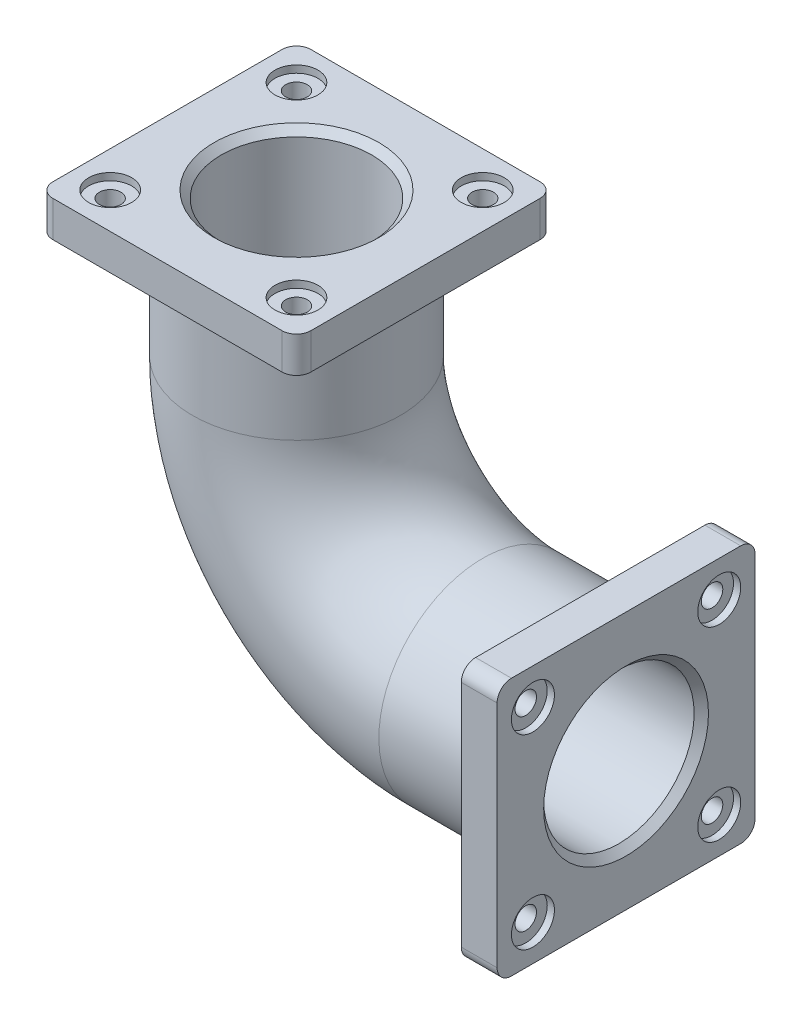
SolidWorks part; units mm, degrees
ref_plane "Front Plane" through (0, 0, 0) normal (0, 0, 1) x (1, 0, 0)
ref_plane "Top Plane" through (0, 0, 0) normal (0, 1, 0) x (1, 0, 0)
ref_plane "Right Plane" through (0, 0, 0) normal (1, 0, 0) x (0, 0, -1)
sketch "Sketch1" plane through (0, 0, 0) normal (0, 0, 1) x (1, 0, 0)
  line L0 (0, 260) -> (0, 410)
  line L1 (260, 0) -> (410, 0)
  line L2 (260, 105) -> (410, 105)
  line L3 (105, 260) -> (105, 410)
  line L4 (260, -105) -> (410, -105)
  line L5 (-105, 260) -> (-105, 410)
  line L6 (-105, 410) -> (105, 410) construction
  line L7 (410, 105) -> (410, -104.7476) construction
  arc A0 (0, 260) -> (260, 0) centre (260, 260) ccw
  arc A1 (105, 260) -> (260, 105) centre (260, 260) ccw
  arc A2 (-105, 260) -> (260, -105) centre (260, 260) ccw
  point P5 (0, 0)
  dimension "D1" = 260
  dimension "D2" = 150
  dimension "D3" = 150
  dimension "D4" = 105
  dimension "D5" = 105
ref_plane "Plane1" through (0, 410, 0) normal (0, 1, 0) x (1, 0, 0)
sketch "Sketch2" plane through (0, 410, 0) normal (0, 1, 0) x (1, 0, 0)
  line L1 (-180, 180) -> (180, 180)
  line L2 (-180, 180) -> (-180, -180)
  line L3 (-180, -180) -> (180, -180)
  line L4 (180, 180) -> (180, -180)
  line L5 (-180, 180) -> (180, -180) construction
  line L6 (-180, -180) -> (180, 180) construction
  circle A0 centre (0, 0) radius 105
  circle A1 centre (0, 0) radius 145
  circle A2 centre (130, 130) radius 30
  circle A3 centre (130, 130) radius 15
  circle A4 centre (130, -130) radius 15
  circle A5 centre (130, -130) radius 30
  circle A6 centre (-130, -130) radius 15
  circle A7 centre (-130, -130) radius 30
  circle A8 centre (-130, 130) radius 15
  circle A9 centre (-130, 130) radius 30
  point P27 (0, 0)
  dimension "D1" = 210
  dimension "D2" = 290
  dimension "D5" = 60
  dimension "D6" = 30
  dimension "D3" = 360
  dimension "D4" = 360
  dimension "D7" = 50
  dimension "D9" = 260
  dimension "D10" = 260
  dimension "D8" = 4
ref_plane "Plane2" through (410, 0, 0) normal (1, 0, 0) x (0, 0, -1)
sketch "Sketch3" plane through (410, 0, 0) normal (1, 0, 0) x (0, 0, -1)
  line L1 (-180, 180) -> (180, 180)
  line L2 (-180, 180) -> (-180, -180)
  line L3 (-180, -180) -> (180, -180)
  line L4 (180, 180) -> (180, -180)
  line L5 (-180, 180) -> (180, -180) construction
  line L6 (-180, -180) -> (180, 180) construction
  circle A0 centre (0, 0) radius 105
  circle A1 centre (0, 0) radius 145
  circle A2 centre (130, 130) radius 30
  circle A3 centre (130, 130) radius 15
  circle A4 centre (130, -130) radius 15
  circle A5 centre (130, -130) radius 30
  circle A6 centre (-130, -130) radius 15
  circle A7 centre (-130, -130) radius 30
  circle A8 centre (-130, 130) radius 15
  circle A9 centre (-130, 130) radius 30
  point P23 (0, 0)
  dimension "D1" = 210
  dimension "D2" = 290
  dimension "D5" = 60
  dimension "D6" = 30
  dimension "D3" = 360
  dimension "D4" = 360
  dimension "D7" = 50
  dimension "D9" = 260
  dimension "D10" = 260
  dimension "D8" = 4
extrude "Boss-Extrude1" add sketch "Sketch3" along normal blind 50 contours L4 L1 L2 L3 A9 A7 A5 A2 A1 | A1 A0 region at (410, 174.9088, 0) region at (410, 0, 140.8988)
extrude "Boss-Extrude2" add sketch "Sketch3<3>" along normal blind 40 contours A9 A8 | A2 A3 | A7 A6 | A5 A4 region at (410, 130, -100.8485) region at (410, -130, -100.8485) region at (410, -130, 159.1515) region at (410, 130, 159.1515)
sketch "Sketch3<3>" plane through (410, 0, 0) normal (1, 0, 0) x (0, 0, -1) same geometry as "Sketch3"
extrude "Boss-Extrude3" add sketch "Sketch2" along normal blind 50 contours L4 L1 L2 L3 A9 A7 A5 A2 A1 | A1 A0 region at (0, 410, -174.9088) region at (-140.8988, 410, 0)
extrude "Boss-Extrude4" add sketch "Sketch2<3>" along normal blind 40 contours A7 A6 | A9 A8 | A5 A4 | A2 A3 region at (100.8485, 410, -130) region at (100.8485, 410, 130) region at (-159.1515, 410, 130) region at (-159.1515, 410, -130)
sketch "Sketch2<3>" plane through (0, 410, 0) normal (0, 1, 0) x (1, 0, 0) same geometry as "Sketch2"
ref_plane "Plane3" through (410, 0, 0) normal (-1, 0, 0) x (0, 0, 1)
sketch "Sketch4" plane through (410, 0, 0) normal (-1, 0, 0) x (0, 0, 1)
  circle A1 centre (0, 0) radius 145
  dimension "D1" = 290
sweep "Sweep1" add profiles "Sketch4" path "Sketch1"
sketch "Sketch5" plane through (0, 410, 0) normal (0, 1, 0) x (1, 0, 0)
  circle A0 centre (0, 0) radius 105 construction
  circle A1 centre (0, 0) radius 105
ref_plane "Plane4" through (0, 0, 0) normal (0, 0, 1) x (1, 0, 0)
sketch "Sketch6" plane through (0, 0, 0) normal (0, 0, 1) x (1, 0, 0)
  line L0 (260, -105) -> (410, -105) construction
  line L1 (-105, 260) -> (-105, 410) construction
  line L2 (260, 105) -> (410, 105) construction
  line L3 (105, 260) -> (105, 410) construction
  line L4 (0, 260) -> (0, 410) construction
  line L5 (260, 0) -> (410, 0) construction
  line L6 (260, -105) -> (410, -105)
  line L7 (-105, 260) -> (-105, 410)
  line L8 (260, 105) -> (410, 105)
  line L9 (105, 260) -> (105, 410)
  line L10 (0, 260) -> (0, 410)
  line L11 (260, 0) -> (410, 0)
  arc A0 (-105, 260) -> (260, -105) centre (260, 260) ccw construction
  arc A1 (105, 260) -> (260, 105) centre (260, 260) ccw construction
  arc A2 (0, 260) -> (260, 0) centre (260, 260) ccw construction
  arc A3 (-105, 260) -> (260, -105) centre (260, 260) ccw
  arc A4 (105, 260) -> (260, 105) centre (260, 260) ccw
  arc A5 (0, 260) -> (260, 0) centre (260, 260) ccw
sweep "Cut-Sweep2" cut profiles "Sketch5" path "Sketch6"
fillet "Chamfer1" radius 10 2 edges at (460, 0, -105) (0, 460, 105) profile chamfer
fillet "Fillet1" radius 20 1 edges at (-180, 435, 180) type face fillet first side face at (0, 435, 180) second side face at (-180, 435, 0)
fillet "Fillet2" radius 20 7 edges at (435, 180, 180) (435, -180, 180) (435, -180, -180) (435, 180, -180) (-180, 435, -180) (180, 435, -180) (180, 435, 180)
